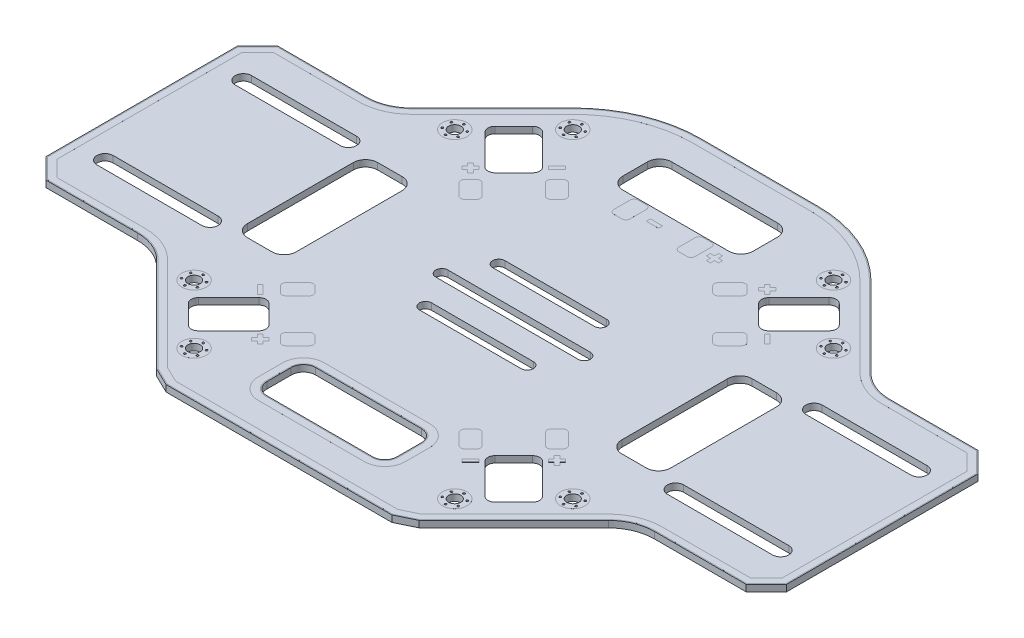
SolidWorks part; units mm, degrees
material "PLA"
ref_plane "Front Plane" through (0, 0, 0) normal (0, 0, 1) x (1, 0, 0)
ref_plane "Top Plane" through (0, 0, 0) normal (0, 1, 0) x (1, 0, 0)
ref_plane "Right Plane" through (0, 0, 0) normal (1, 0, 0) x (0, 0, -1)
sketch "Sketch1" plane through (0, 0, 0) normal (0, 1, 0) x (1, 0, 0)
  line L0 (0, 60.3186) -> (0, -57.6814) construction
  line L1 (-27.75, -57.6814) -> (27.75, -57.6814)
  line L2 (-13, -47.6814) -> (13, -47.6814)
  line L3 (-16, -38.6814) -> (-16, -44.6814)
  line L4 (16, -38.6814) -> (16, -44.6814)
  line L5 (-16, -41.6814) -> (16, -41.6814) construction
  line L6 (-13, -35.6814) -> (13, -35.6814)
  line L7 (-27.75, -57.6814) -> (-32.25, -55.502)
  line L8 (27.75, -57.6814) -> (32.25, -55.502)
  line L9 (-32.25, -55.502) -> (32.25, -55.502) construction
  line L10 (32.25, -55.502) -> (55.502, -32.25)
  line L11 (-32.25, -55.502) -> (-55.502, -32.25)
  line L12 (-43.876, 43.876) -> (43.876, -43.876) construction
  line L13 (-43.876, -43.876) -> (43.876, 43.876) construction
  line L14 (37.6888, -42.285) -> (42.285, -37.6888)
  line L15 (27.7893, -34.8604) -> (35.2139, -42.285)
  line L16 (34.8604, -27.7893) -> (42.285, -35.2139)
  line L17 (31.5016, -38.5727) -> (38.5727, -31.5016) construction
  line L18 (27.7893, -32.3855) -> (32.3855, -27.7893)
  line L19 (-38.5727, -31.5016) -> (-31.5016, -38.5727) construction
  line L20 (-35.2139, -42.285) -> (-27.7893, -34.8604)
  line L21 (-42.285, -35.2139) -> (-34.8604, -27.7893)
  line L22 (-32.3855, -27.7893) -> (-27.7893, -32.3855)
  line L23 (-42.285, -37.6888) -> (-37.6888, -42.285)
  line L24 (-63.5, -28.9371) -> (63.5, -28.9371) construction
  line L25 (63.5, -28.9371) -> (86, -28.9371)
  line L26 (-63.5, -28.9371) -> (-86, -28.9371)
  line L27 (-91, -23.9371) -> (-91, 23.0629)
  line L28 (91, -23.9371) -> (91, 23.0629)
  line L29 (-86, -28.9371) -> (-86, 28.0629) construction
  line L30 (86, -28.9371) -> (86, 28.0629) construction
  line L31 (-91, -0.4371) -> (-86, -0.4371) construction
  line L32 (86, -0.4371) -> (91, -0.4371) construction
  line L33 (86, -28.9371) -> (91, -23.9371)
  line L34 (-91, -23.9371) -> (-86, -28.9371)
  line L35 (91, 23.0629) -> (86, 28.0629)
  line L36 (-91, 23.0629) -> (-86, 28.0629)
  line L37 (-56.4271, 31.3248) -> (-36.6281, 51.1238)
  line L38 (36.6281, 51.1238) -> (56.4271, 31.3248)
  line L39 (-35.2139, 42.285) -> (-27.7893, 34.8604)
  line L40 (-36.6281, 51.1238) -> (-27.7893, 42.285) construction
  line L41 (-27.7893, 42.285) -> (-31.5016, 38.5727) construction
  line L42 (-42.285, 35.2139) -> (-34.8604, 27.7893)
  line L43 (-31.5016, 38.5727) -> (-38.5727, 31.5016) construction
  line L44 (-42.285, 37.6888) -> (-37.6888, 42.285)
  line L45 (-32.3855, 27.7893) -> (-27.7893, 32.3855)
  line L46 (-86, 28.0629) -> (-64.3021, 28.0629)
  line L47 (86, 28.0629) -> (64.3021, 28.0629)
  line L48 (37.6888, 42.285) -> (42.285, 37.6888)
  line L49 (27.7893, 32.3855) -> (32.3855, 27.7893)
  line L50 (27.7893, 34.8604) -> (35.2139, 42.285)
  line L51 (34.8604, 27.7893) -> (42.285, 35.2139)
  line L52 (31.5016, 38.5727) -> (38.5727, 31.5016) construction
  line L53 (31.5016, 38.5727) -> (27.7893, 42.285) construction
  line L54 (27.7893, 42.285) -> (36.6281, 51.1238) construction
  line L55 (-14.43, 60.3186) -> (14.43, 60.3186)
  line L56 (-13, 51.8186) -> (13, 51.8186)
  line L57 (-13, 39.8186) -> (13, 39.8186)
  line L58 (16, 48.8186) -> (16, 42.8186)
  line L59 (-16, 48.8186) -> (-16, 42.8186)
  line L60 (-12.5, -10.6814) -> (12.5, -10.6814)
  line L61 (-12.5, -7.6814) -> (12.5, -7.6814)
  line L62 (-17.5, -1.6814) -> (17.5, -1.6814)
  line L63 (-17.5, 1.3186) -> (17.5, 1.3186)
  line L64 (-12.5, 7.3186) -> (12.5, 7.3186)
  line L65 (-12.5, 10.3186) -> (12.5, 10.3186)
  line L66 (-52, 12.5629) -> (-52, -13.4371)
  line L67 (-86, -0.4371) -> (-52, -0.4371) construction
  line L68 (-40, 12.5629) -> (-40, -13.4371)
  line L69 (52, 12.5629) -> (52, -13.4371)
  line L70 (-49, 15.5629) -> (-43, 15.5629)
  line L71 (-49, -16.4371) -> (-43, -16.4371)
  line L72 (86, -0.4371) -> (52, -0.4371) construction
  line L73 (40, 12.5629) -> (40, -13.4371)
  line L74 (43, 15.5629) -> (49, 15.5629)
  line L75 (43, -16.4371) -> (49, -16.4371)
  line L76 (-83, 18.5629) -> (-57.2, 18.5629)
  line L77 (-83, 14.5629) -> (-57.2, 14.5629)
  line L78 (-83, -15.4371) -> (-57.2, -15.4371)
  line L79 (-83, -19.4371) -> (-57.2, -19.4371)
  line L80 (57.2, -15.4371) -> (83, -15.4371)
  line L81 (57.2, -19.4371) -> (83, -19.4371)
  line L82 (57.2, 18.5629) -> (83, 18.5629)
  line L83 (57.2, 14.5629) -> (83, 14.5629)
  line L84 (-46.5276, 32.0319) -> (-32.0319, 46.5276) construction
  line L85 (32.0319, -46.5276) -> (46.5276, -32.0319) construction
  arc A0 (-16, -44.6814) -> (-13, -47.6814) centre (-13, -44.6814) ccw
  arc A1 (-13, -35.6814) -> (-16, -38.6814) centre (-13, -38.6814) ccw
  arc A2 (16, -38.6814) -> (13, -35.6814) centre (13, -38.6814) ccw
  arc A3 (13, -47.6814) -> (16, -44.6814) centre (13, -44.6814) ccw
  arc A4 (27.7893, -32.3855) -> (27.7893, -34.8604) centre (29.0267, -33.6229) ccw
  arc A5 (34.8604, -27.7893) -> (32.3855, -27.7893) centre (33.6229, -29.0267) ccw
  arc A6 (35.2139, -42.285) -> (37.6888, -42.285) centre (36.4514, -41.0475) ccw
  arc A7 (42.285, -37.6888) -> (42.285, -35.2139) centre (41.0475, -36.4514) ccw
  arc A8 (-37.6888, -42.285) -> (-35.2139, -42.285) centre (-36.4514, -41.0475) ccw
  arc A9 (-42.285, -35.2139) -> (-42.285, -37.6888) centre (-41.0475, -36.4514) ccw
  arc A10 (-32.3855, -27.7893) -> (-34.8604, -27.7893) centre (-33.6229, -29.0267) ccw
  arc A11 (-27.7893, -34.8604) -> (-27.7893, -32.3855) centre (-29.0267, -33.6229) ccw
  arc A12 (-55.502, -32.25) -> (-63.5, -28.9371) centre (-63.5, -40.248) ccw
  arc A13 (63.5, -28.9371) -> (55.502, -32.25) centre (63.5, -40.248) ccw
  arc A14 (-42.285, 37.6888) -> (-42.285, 35.2139) centre (-41.0475, 36.4514) ccw
  arc A15 (-35.2139, 42.285) -> (-37.6888, 42.285) centre (-36.4514, 41.0475) ccw
  arc A16 (-27.7893, 32.3855) -> (-27.7893, 34.8604) centre (-29.0267, 33.6229) ccw
  arc A17 (-34.8604, 27.7893) -> (-32.3855, 27.7893) centre (-33.6229, 29.0267) ccw
  arc A18 (-64.3021, 28.0629) -> (-56.4271, 31.3248) centre (-64.3021, 39.1998) ccw
  arc A19 (56.4271, 31.3248) -> (64.3021, 28.0629) centre (64.3021, 39.1998) ccw
  arc A20 (27.7893, 34.8604) -> (27.7893, 32.3855) centre (29.0267, 33.6229) ccw
  arc A21 (37.6888, 42.285) -> (35.2139, 42.285) centre (36.4514, 41.0475) ccw
  arc A22 (42.285, 35.2139) -> (42.285, 37.6888) centre (41.0475, 36.4514) ccw
  arc A23 (32.3855, 27.7893) -> (34.8604, 27.7893) centre (33.6229, 29.0267) ccw
  arc A24 (-14.43, 60.3186) -> (-36.6281, 51.1238) centre (-14.43, 28.9257) ccw
  arc A25 (13, 39.8186) -> (16, 42.8186) centre (13, 42.8186) ccw
  arc A26 (36.6281, 51.1238) -> (14.43, 60.3186) centre (14.43, 28.9257) ccw
  arc A27 (16, 48.8186) -> (13, 51.8186) centre (13, 48.8186) ccw
  arc A28 (-16, 42.8186) -> (-13, 39.8186) centre (-13, 42.8186) ccw
  arc A29 (-13, 51.8186) -> (-16, 48.8186) centre (-13, 48.8186) ccw
  arc A30 (-12.5, -7.6814) -> (-12.5, -10.6814) centre (-12.5, -9.1814) ccw
  arc A31 (12.5, -10.6814) -> (12.5, -7.6814) centre (12.5, -9.1814) ccw
  arc A32 (-17.5, 1.3186) -> (-17.5, -1.6814) centre (-17.5, -0.1814) ccw
  arc A33 (17.5, -1.6814) -> (17.5, 1.3186) centre (17.5, -0.1814) ccw
  arc A34 (-12.5, 10.3186) -> (-12.5, 7.3186) centre (-12.5, 8.8186) ccw
  arc A35 (12.5, 7.3186) -> (12.5, 10.3186) centre (12.5, 8.8186) ccw
  arc A36 (-49, 15.5629) -> (-52, 12.5629) centre (-49, 12.5629) ccw
  arc A37 (-40, 12.5629) -> (-43, 15.5629) centre (-43, 12.5629) ccw
  arc A38 (-52, -13.4371) -> (-49, -16.4371) centre (-49, -13.4371) ccw
  arc A39 (-43, -16.4371) -> (-40, -13.4371) centre (-43, -13.4371) ccw
  arc A40 (43, 15.5629) -> (40, 12.5629) centre (43, 12.5629) ccw
  arc A41 (52, 12.5629) -> (49, 15.5629) centre (49, 12.5629) ccw
  arc A42 (40, -13.4371) -> (43, -16.4371) centre (43, -13.4371) ccw
  arc A43 (49, -16.4371) -> (52, -13.4371) centre (49, -13.4371) ccw
  arc A44 (-57.2, 14.5629) -> (-57.2, 18.5629) centre (-57.2, 16.5629) ccw
  arc A45 (-83, 18.5629) -> (-83, 14.5629) centre (-83, 16.5629) ccw
  arc A46 (-83, -15.4371) -> (-83, -19.4371) centre (-83, -17.4371) ccw
  arc A47 (-57.2, -19.4371) -> (-57.2, -15.4371) centre (-57.2, -17.4371) ccw
  arc A48 (57.2, -15.4371) -> (57.2, -19.4371) centre (57.2, -17.4371) ccw
  arc A49 (83, -19.4371) -> (83, -15.4371) centre (83, -17.4371) ccw
  arc A50 (57.2, 18.5629) -> (57.2, 14.5629) centre (57.2, 16.5629) ccw
  arc A51 (83, 14.5629) -> (83, 18.5629) centre (83, 16.5629) ccw
  circle A52 centre (-32.0319, 46.5276) radius 1.5
  circle A53 centre (-46.5276, 32.0319) radius 1.5
  circle A54 centre (32.0319, -46.5276) radius 1.5
  circle A55 centre (46.5276, -32.0319) radius 1.5
  circle A56 centre (-46.5276, -32.0319) radius 1.5
  circle A57 centre (-32.0319, -46.5276) radius 1.5
  circle A58 centre (32.0319, 46.5276) radius 1.5
  circle A59 centre (46.5276, 32.0319) radius 1.5
  point P4 (-35.0371, 35.0371)
  point P5 (0, -47.6814)
  point P14 (0, -41.6814)
  point P15 (0, -35.6814)
  point P19 (0, -55.502)
  point P29 (0, 0)
  point P30 (39.9869, -39.9869)
  point P32 (0, 0)
  point P42 (30.0874, -30.0874)
  point P43 (35.0371, -35.0371)
  point P50 (-35.0371, -35.0371)
  point P53 (-38.5727, -31.5016)
  point P62 (-39.9869, -39.9869)
  point P63 (-30.0874, -30.0874)
  point P70 (0, -28.9371)
  point P99 (-39.9869, 39.9869)
  point P102 (-30.0874, 30.0874)
  point P119 (35.0371, 35.0371)
  point P122 (39.9869, 39.9869)
  point P123 (30.0874, 30.0874)
  point P135 (0, 51.8186)
  point P138 (0, 39.8186)
  point P147 (0, -10.6814)
  point P151 (-14, -9.1814)
  point P153 (14, -9.1814)
  point P156 (0, -1.6814)
  point P158 (-19, -0.1814)
  point P162 (19, -0.1814)
  point P167 (0, 7.3186)
  point P203 (-85, 16.5629)
  point P205 (-55.2, 16.5629)
  point P217 (85, -17.4371)
  point P229 (-39.2798, 39.2798)
  point P232 (39.2798, -39.2798)
  dimension "D5" = 12
  dimension "D6" = 55.5
  dimension "D14" = 14
  dimension "D15" = 127
  dimension "D16" = 22.5
  dimension "D23" = 8.5
  dimension "D24" = 25
  dimension "D25" = 3
  dimension "D28" = 3
  dimension "D31" = 39
  dimension "D32" = 9.5
  dimension "D34" = 29.8
  dimension "D38" = 6
  dimension "D39" = 3
  dimension "D1" = 118
  dimension "D2" = 10
  dimension "D3" = 32
  dimension "D4" = 6
  dimension "D7" = 64.5
  dimension "D8" = 5
  dimension "D9" = 124.1
  dimension "D10" = 45
  dimension "D11" = 5.5
  dimension "D12" = 6.5
  dimension "D13" = 10
  dimension "D17" = 22.5
  dimension "D18" = 5
  dimension "D19" = 45
  dimension "D20" = 47
  dimension "D21" = 28
  dimension "D22" = 5.25
  dimension "D26" = 28
  dimension "D27" = 6
  dimension "D29" = 38
  dimension "D30" = 6
  dimension "D33" = 4
  dimension "D35" = 6
  dimension "D36" = 9.5
  dimension "D37" = 4
  dimension "D40" = 6.5
  dimension "D41" = 6.5
extrude "Boss-Extrude1" add sketch "Sketch1" along normal blind 0.8 and the other way blind 0.8
sketch "Sketch2" plane through (0, 0.8, 0) normal (0, 1, 0) x (1, 0, 0)
  line L0 (-27.6926, -57.4314) -> (27.6926, -57.4314)
  line L1 (-27.75, -57.6814) -> (27.75, -57.6814) construction
  line L2 (-27.6926, -57.4314) -> (-32.1031, -55.2953)
  line L3 (-32.25, -55.502) -> (-27.75, -57.6814) construction
  line L4 (27.6926, -57.4314) -> (32.1031, -55.2953)
  line L5 (27.75, -57.6814) -> (32.25, -55.502) construction
  line L6 (0, -57.6814) -> (0, -57.4314) construction
  line L7 (-32.1031, -55.2953) -> (-55.3252, -32.0732)
  line L8 (-55.502, -32.25) -> (-32.25, -55.502) construction
  line L9 (32.1031, -55.2953) -> (55.3252, -32.0732)
  line L10 (32.25, -55.502) -> (55.502, -32.25) construction
  line L11 (-85.8964, -28.6871) -> (-63.5, -28.6871)
  line L12 (-85.8964, -28.6871) -> (-90.75, -23.8335)
  line L13 (-91, -23.9371) -> (-86, -28.9371) construction
  line L14 (-86, -28.9371) -> (-63.5, -28.9371) construction
  line L15 (63.5, -28.6871) -> (85.8964, -28.6871)
  line L16 (85.8964, -28.6871) -> (90.75, -23.8335)
  line L17 (-90.75, -23.8335) -> (-90.75, 22.9593)
  line L18 (-91, 23.0629) -> (-91, -23.9371) construction
  line L19 (-90.75, 22.9593) -> (-85.8964, 27.8129)
  line L20 (-85.8964, 27.8129) -> (-64.3021, 27.8129)
  line L21 (-64.3021, 28.0629) -> (-86, 28.0629) construction
  line L22 (-56.2503, 31.1481) -> (-36.4514, 50.947)
  line L23 (-36.6281, 51.1238) -> (-56.4271, 31.3248) construction
  line L24 (-14.43, 60.0686) -> (14.43, 60.0686)
  line L25 (14.43, 60.3186) -> (-14.43, 60.3186) construction
  line L26 (56.2503, 31.1481) -> (36.4514, 50.947)
  line L27 (56.4271, 31.3248) -> (36.6281, 51.1238) construction
  line L28 (64.3021, 27.8129) -> (85.8964, 27.8129)
  line L29 (86, 28.0629) -> (64.3021, 28.0629) construction
  line L30 (85.8964, 27.8129) -> (90.75, 22.9593)
  line L31 (91, 23.0629) -> (86, 28.0629) construction
  line L32 (90.75, 22.9593) -> (90.75, -23.8335)
  line L33 (-55.0836, 29.9813) -> (-35.2846, 49.7803)
  line L34 (-14.43, 58.4186) -> (14.43, 58.4186)
  line L35 (55.0836, 29.9813) -> (35.2846, 49.7803)
  line L36 (64.3021, 26.1629) -> (85.213, 26.1629)
  line L37 (85.213, 26.1629) -> (89.1, 22.2759)
  line L38 (89.1, 22.2759) -> (89.1, -23.1501)
  line L39 (85.213, -27.0371) -> (89.1, -23.1501)
  line L40 (63.5, -27.0371) -> (85.213, -27.0371)
  line L41 (31.1332, -53.9317) -> (54.1584, -30.9065)
  line L42 (27.3141, -55.7814) -> (31.1332, -53.9317)
  line L43 (-27.3141, -55.7814) -> (27.3141, -55.7814)
  line L44 (-27.3141, -55.7814) -> (-31.1332, -53.9317)
  line L45 (-31.1332, -53.9317) -> (-54.1584, -30.9065)
  line L46 (-85.213, -27.0371) -> (-63.5, -27.0371)
  line L47 (-85.213, -27.0371) -> (-89.1, -23.1501)
  line L48 (-89.1, -23.1501) -> (-89.1, 22.2759)
  line L49 (-89.1, 22.2759) -> (-85.213, 26.1629)
  line L50 (-85.213, 26.1629) -> (-64.3021, 26.1629)
  line L51 (-13, -35.4314) -> (13, -35.4314)
  line L52 (-16.25, -38.6814) -> (-16.25, -44.6814)
  line L53 (-13, -47.9314) -> (13, -47.9314)
  line L54 (16.25, -44.6814) -> (16.25, -38.6814)
  line L55 (16, -44.6814) -> (16, -38.6814) construction
  line L56 (13, -35.6814) -> (-13, -35.6814) construction
  line L57 (-16, -38.6814) -> (-16, -44.6814) construction
  line L58 (-13, -47.6814) -> (13, -47.6814) construction
  line L59 (-13, -33.6314) -> (13, -33.6314)
  line L60 (18.05, -44.6814) -> (18.05, -38.6814)
  line L61 (-13, -49.7314) -> (13, -49.7314)
  line L62 (-18.05, -38.6814) -> (-18.05, -44.6814)
  line L63 (32.0319, -43.5276) -> (32.0319, -44.2776) construction
  line L64 (-32.0319, -44.2776) -> (-33.9805, -45.4026) construction
  line L65 (-33.9805, -45.4026) -> (-33.9805, -47.6526) construction
  line L66 (-33.9805, -47.6526) -> (-32.0319, -48.7776) construction
  line L67 (-32.0319, -48.7776) -> (-30.0834, -47.6526) construction
  line L68 (-30.0834, -47.6526) -> (-30.0834, -45.4026) construction
  line L69 (-30.0834, -45.4026) -> (-32.0319, -44.2776) construction
  line L70 (-46.5276, -29.7819) -> (-48.4762, -30.9069) construction
  line L71 (-48.4762, -30.9069) -> (-48.4762, -33.1569) construction
  line L72 (-48.4762, -33.1569) -> (-46.5276, -34.2819) construction
  line L73 (-46.5276, -34.2819) -> (-44.5791, -33.1569) construction
  line L74 (-44.5791, -33.1569) -> (-44.5791, -30.9069) construction
  line L75 (-44.5791, -30.9069) -> (-46.5276, -29.7819) construction
  line L76 (-46.5276, 34.2819) -> (-48.4762, 33.1569) construction
  line L77 (-48.4762, 33.1569) -> (-48.4762, 30.9069) construction
  line L78 (-48.4762, 30.9069) -> (-46.5276, 29.7819) construction
  line L79 (-46.5276, 29.7819) -> (-44.5791, 30.9069) construction
  line L80 (-44.5791, 30.9069) -> (-44.5791, 33.1569) construction
  line L81 (-44.5791, 33.1569) -> (-46.5276, 34.2819) construction
  line L82 (-32.0319, 48.7776) -> (-33.9805, 47.6526) construction
  line L83 (-33.9805, 47.6526) -> (-33.9805, 45.4026) construction
  line L84 (-33.9805, 45.4026) -> (-32.0319, 44.2776) construction
  line L85 (-32.0319, 44.2776) -> (-30.0834, 45.4026) construction
  line L86 (-30.0834, 45.4026) -> (-30.0834, 47.6526) construction
  line L87 (-30.0834, 47.6526) -> (-32.0319, 48.7776) construction
  line L88 (32.0319, 48.7776) -> (30.0834, 47.6526) construction
  line L89 (30.0834, 47.6526) -> (30.0834, 45.4026) construction
  line L90 (30.0834, 45.4026) -> (32.0319, 44.2776) construction
  line L91 (32.0319, 44.2776) -> (33.9805, 45.4026) construction
  line L92 (33.9805, 45.4026) -> (33.9805, 47.6526) construction
  line L93 (33.9805, 47.6526) -> (32.0319, 48.7776) construction
  line L94 (46.5276, 34.2819) -> (44.5791, 33.1569) construction
  line L95 (44.5791, 33.1569) -> (44.5791, 30.9069) construction
  line L96 (44.5791, 30.9069) -> (46.5276, 29.7819) construction
  line L97 (46.5276, 29.7819) -> (48.4762, 30.9069) construction
  line L98 (48.4762, 30.9069) -> (48.4762, 33.1569) construction
  line L99 (48.4762, 33.1569) -> (46.5276, 34.2819) construction
  line L100 (46.5276, -29.7819) -> (44.5791, -30.9069) construction
  line L101 (44.5791, -30.9069) -> (44.5791, -33.1569) construction
  line L102 (44.5791, -33.1569) -> (46.5276, -34.2819) construction
  line L103 (46.5276, -34.2819) -> (48.4762, -33.1569) construction
  line L104 (48.4762, -33.1569) -> (48.4762, -30.9069) construction
  line L105 (48.4762, -30.9069) -> (46.5276, -29.7819) construction
  line L106 (32.0319, -44.2776) -> (30.0834, -45.4026) construction
  line L107 (30.0834, -45.4026) -> (30.0834, -47.6526) construction
  line L108 (30.0834, -47.6526) -> (32.0319, -48.7776) construction
  line L109 (32.0319, -48.7776) -> (33.9805, -47.6526) construction
  line L110 (33.9805, -47.6526) -> (33.9805, -45.4026) construction
  line L111 (33.9805, -45.4026) -> (32.0319, -44.2776) construction
  line L112 (32.0319, -44.2776) -> (32.0319, -45.0276) construction
  arc A0 (-55.3252, -32.0732) -> (-63.5, -28.6871) centre (-63.5, -40.248) ccw
  arc A1 (-55.502, -32.25) -> (-63.5, -28.9371) centre (-63.5, -40.248) ccw construction
  arc A2 (63.5, -28.6871) -> (55.3252, -32.0732) centre (63.5, -40.248) ccw
  arc A3 (63.5, -28.9371) -> (55.502, -32.25) centre (63.5, -40.248) ccw construction
  arc A4 (-64.3021, 27.8129) -> (-56.2503, 31.1481) centre (-64.3021, 39.1998) ccw
  arc A5 (-64.3021, 28.0629) -> (-56.4271, 31.3248) centre (-64.3021, 39.1998) ccw construction
  arc A6 (-14.43, 60.0686) -> (-36.4514, 50.947) centre (-14.43, 28.9257) ccw
  arc A7 (-14.43, 60.3186) -> (-36.6281, 51.1238) centre (-14.43, 28.9257) ccw construction
  arc A8 (36.4514, 50.947) -> (14.43, 60.0686) centre (14.43, 28.9257) ccw
  arc A9 (36.6281, 51.1238) -> (14.43, 60.3186) centre (14.43, 28.9257) ccw construction
  arc A10 (56.2503, 31.1481) -> (64.3021, 27.8129) centre (64.3021, 39.1998) ccw
  arc A11 (56.4271, 31.3248) -> (64.3021, 28.0629) centre (64.3021, 39.1998) ccw construction
  arc A12 (-14.43, 58.4186) -> (-35.2846, 49.7803) centre (-14.43, 28.9257) ccw
  arc A13 (35.2846, 49.7803) -> (14.43, 58.4186) centre (14.43, 28.9257) ccw
  arc A14 (55.0836, 29.9813) -> (64.3021, 26.1629) centre (64.3021, 39.1998) ccw
  arc A15 (63.5, -27.0371) -> (54.1584, -30.9065) centre (63.5, -40.248) ccw
  arc A16 (-54.1584, -30.9065) -> (-63.5, -27.0371) centre (-63.5, -40.248) ccw
  arc A17 (-64.3021, 26.1629) -> (-55.0836, 29.9813) centre (-64.3021, 39.1998) ccw
  arc A18 (-13, -35.4314) -> (-16.25, -38.6814) centre (-13, -38.6814) ccw
  arc A19 (16.25, -38.6814) -> (13, -35.4314) centre (13, -38.6814) ccw
  arc A20 (-16.25, -44.6814) -> (-13, -47.9314) centre (-13, -44.6814) ccw
  arc A21 (13, -47.9314) -> (16.25, -44.6814) centre (13, -44.6814) ccw
  arc A22 (-13, -35.6814) -> (-16, -38.6814) centre (-13, -38.6814) ccw construction
  arc A23 (-16, -44.6814) -> (-13, -47.6814) centre (-13, -44.6814) ccw construction
  arc A24 (16, -38.6814) -> (13, -35.6814) centre (13, -38.6814) ccw construction
  arc A25 (13, -47.6814) -> (16, -44.6814) centre (13, -44.6814) ccw construction
  arc A26 (18.05, -38.6814) -> (13, -33.6314) centre (13, -38.6814) ccw
  arc A27 (13, -49.7314) -> (18.05, -44.6814) centre (13, -44.6814) ccw
  arc A28 (-18.05, -44.6814) -> (-13, -49.7314) centre (-13, -44.6814) ccw
  arc A29 (-13, -33.6314) -> (-18.05, -38.6814) centre (-13, -38.6814) ccw
  circle A30 centre (-32.0319, -46.5276) radius 1.5
  circle A31 centre (-46.5276, -32.0319) radius 1.5
  circle A32 centre (-46.5276, 32.0319) radius 1.5
  circle A33 centre (-32.0319, 46.5276) radius 1.5
  circle A34 centre (32.0319, 46.5276) radius 1.5
  circle A35 centre (46.5276, 32.0319) radius 1.5
  circle A36 centre (46.5276, -32.0319) radius 1.5
  circle A37 centre (32.0319, -46.5276) radius 1.5
  circle A38 centre (-32.0319, -46.5276) radius 1.5 construction
  circle A39 centre (-46.5276, -32.0319) radius 1.5 construction
  circle A40 centre (-46.5276, 32.0319) radius 1.5 construction
  circle A41 centre (-32.0319, 46.5276) radius 1.5 construction
  circle A42 centre (32.0319, 46.5276) radius 1.5 construction
  circle A43 centre (46.5276, 32.0319) radius 1.5 construction
  circle A44 centre (46.5276, -32.0319) radius 1.5 construction
  circle A45 centre (32.0319, -46.5276) radius 1.5 construction
  circle A46 centre (-32.0319, -46.5276) radius 3
  circle A47 centre (-46.5276, -32.0319) radius 3
  circle A48 centre (-46.5276, 32.0319) radius 3
  circle A49 centre (-32.0319, 46.5276) radius 3
  circle A50 centre (32.0319, 46.5276) radius 3
  circle A51 centre (46.5276, 32.0319) radius 3
  circle A52 centre (46.5276, -32.0319) radius 3
  circle A53 centre (32.0319, -46.5276) radius 3
  circle A54 centre (-32.0319, -46.5276) radius 1.9486 construction
  circle A55 centre (-46.5276, -32.0319) radius 1.9486 construction
  circle A56 centre (-46.5276, 32.0319) radius 1.9486 construction
  circle A57 centre (-32.0319, 46.5276) radius 1.9486 construction
  circle A58 centre (32.0319, 46.5276) radius 1.9486 construction
  circle A59 centre (46.5276, 32.0319) radius 1.9486 construction
  circle A60 centre (46.5276, -32.0319) radius 1.9486 construction
  circle A61 centre (32.0319, -46.5276) radius 1.9486 construction
  circle A62 centre (32.0319, -44.2776) radius 0.25
  circle A63 centre (33.9805, -45.4026) radius 0.25
  circle A64 centre (33.9805, -47.6526) radius 0.25
  circle A65 centre (32.0319, -48.7776) radius 0.25
  circle A66 centre (30.0834, -47.6526) radius 0.25
  circle A67 centre (30.0834, -45.4026) radius 0.25
  circle A68 centre (46.5276, -34.2819) radius 0.25
  circle A69 centre (48.4762, -33.1569) radius 0.25
  circle A70 centre (48.4762, -30.9069) radius 0.25
  circle A71 centre (46.5276, -29.7819) radius 0.25
  circle A72 centre (44.5791, -30.9069) radius 0.25
  circle A73 centre (44.5791, -33.1569) radius 0.25
  circle A74 centre (46.5276, 29.7819) radius 0.25
  circle A75 centre (48.4762, 30.9069) radius 0.25
  circle A76 centre (48.4762, 33.1569) radius 0.25
  circle A77 centre (46.5276, 34.2819) radius 0.25
  circle A78 centre (44.5791, 33.1569) radius 0.25
  circle A79 centre (44.5791, 30.9069) radius 0.25
  circle A80 centre (32.0319, 44.2776) radius 0.25
  circle A81 centre (33.9805, 45.4026) radius 0.25
  circle A82 centre (33.9805, 47.6526) radius 0.25
  circle A83 centre (32.0319, 48.7776) radius 0.25
  circle A84 centre (30.0834, 47.6526) radius 0.25
  circle A85 centre (30.0834, 45.4026) radius 0.25
  circle A86 centre (-32.0319, 48.7776) radius 0.25
  circle A87 centre (-30.0834, 47.6526) radius 0.25
  circle A88 centre (-30.0834, 45.4026) radius 0.25
  circle A89 centre (-32.0319, 44.2776) radius 0.25
  circle A90 centre (-33.9805, 47.6526) radius 0.25
  circle A91 centre (-33.9805, 45.4026) radius 0.25
  circle A92 centre (-46.5276, 29.7819) radius 0.25
  circle A93 centre (-44.5791, 30.9069) radius 0.25
  circle A94 centre (-44.5791, 33.1569) radius 0.25
  circle A95 centre (-46.5276, 34.2819) radius 0.25
  circle A96 centre (-48.4762, 33.1569) radius 0.25
  circle A97 centre (-48.4762, 30.9069) radius 0.25
  circle A98 centre (-46.5276, -29.7819) radius 0.25
  circle A99 centre (-44.5791, -30.9069) radius 0.25
  circle A100 centre (-44.5791, -33.1569) radius 0.25
  circle A101 centre (-46.5276, -34.2819) radius 0.25
  circle A102 centre (-48.4762, -33.1569) radius 0.25
  circle A103 centre (-48.4762, -30.9069) radius 0.25
  circle A104 centre (-32.0319, -44.2776) radius 0.25
  circle A105 centre (-30.0834, -45.4026) radius 0.25
  circle A106 centre (-30.0834, -47.6526) radius 0.25
  circle A107 centre (-32.0319, -48.7776) radius 0.25
  circle A108 centre (-33.9805, -47.6526) radius 0.25
  circle A109 centre (-33.9805, -45.4026) radius 0.25
  dimension "D2" = 0.25
  dimension "D5" = 0.25
  dimension "D7" = 1.65
  dimension "D8" = 0.25
  dimension "D10" = 6
  dimension "D11" = 0.5
  dimension "D1" = 0.25
  dimension "D3" = 0.25
  dimension "D4" = 0.25
  dimension "D6" = 0.25
  dimension "D9" = 1.8
extrude "Boss-Extrude2" add sketch "Sketch2" along normal blind 0.001 contours A10 L26 A8 L24 A6 L22 A4 L20 L19 L17 L12 L11 A0 L7 L2 L0 L4 L9 A2 L15 L16 L32 L30 L28 L50 A17 L33 A12 L34 A13 L35 A14 L36 L37 L38 L39 L40 A15 L41 L42 L43 L44 L45 A16 L46 L47 L48 L49 | A46 A109 A108 A107 A106 A105 A104 A30 | A47 A103 A102 A101 A100 A99 A98 A31 | A48 A97 A96 A95 A94 A93 A92 A32 | A49 A91 A90 A89 A88 A87 A86 A33 | A50 A85 A84 A83 A82 A81 A80 A34 | A51 A79 A78 A77 A76 A75 A74 A35 | A52 A73 A72 A71 A70 A69 A68 A36 | A53 A67 A66 A65 A64 A63 A62 A37 | L59 A29 L62 A28 L61 A27 L60 A26 A21 L53 A20 L52 A18 L51 A19 L54 region at (-29.8036, 0.8, 56.1688) region at (0, 0.8, 34.0267) region at (-34.9471, 0.8, 46.5276) region at (-49.4428, 0.8, 32.0319) region at (-49.4428, 0.8, -32.0319) region at (-34.9471, 0.8, -46.5276) region at (29.1168, 0.8, -46.5276) region at (43.6125, 0.8, -32.0319) region at (43.6125, 0.8, 32.0319) region at (29.1168, 0.8, 46.5276)
mirror "Mirror1" about plane through (0, 0, 0) normal (0, 1, 0) of "Boss-Extrude2"
sketch "Sketch5" plane through (0, 0.8, 0) normal (0, 1, 0) x (1, 0, 0)
  line L0 (35.7442, -27.259) -> (36.4514, -26.5519)
  line L1 (35.0371, -26.5519) -> (35.7442, -25.8448)
  line L2 (35.3907, -26.9054) -> (37.512, -24.7841) construction
  line L3 (35.0371, -26.5519) -> (35.7442, -27.259)
  line L4 (37.1585, -24.4305) -> (37.8656, -25.1376)
  line L5 (42.285, -35.2139) -> (34.8604, -27.7893) construction
  line L6 (32.1031, -55.2953) -> (55.3252, -32.0732) construction
  line L8 (35.3907, -24.7841) -> (37.512, -26.9054) construction
  line L9 (35.0371, -25.1376) -> (35.7442, -24.4305)
  line L10 (37.1585, -27.259) -> (37.8656, -26.5519)
  line L11 (35.0371, -25.1376) -> (35.7442, -25.8448)
  line L12 (35.7442, -24.4305) -> (36.4514, -25.1376)
  line L13 (36.4514, -26.5519) -> (37.1585, -27.259)
  line L14 (36.4514, -25.1376) -> (37.1585, -24.4305)
  line L15 (37.1585, -25.8448) -> (37.8656, -26.5519)
  line L16 (37.1585, -25.8448) -> (37.8656, -25.1376)
  line L17 (26.9054, -35.3907) -> (24.7841, -37.512) construction
  line L18 (26.5519, -35.0371) -> (27.259, -35.7442)
  line L19 (27.7893, -34.8604) -> (35.2139, -42.285) construction
  line L20 (24.4305, -37.1585) -> (25.1376, -37.8656)
  line L21 (24.4305, -37.1585) -> (26.5519, -35.0371)
  line L22 (25.1376, -37.8656) -> (27.259, -35.7442)
  line L23 (-37.1585, -24.4305) -> (-37.8656, -25.1376)
  line L24 (-37.1585, -24.4305) -> (-35.0371, -26.5519)
  line L25 (-37.8656, -25.1376) -> (-35.7442, -27.259)
  line L26 (-35.3907, -26.9054) -> (-37.512, -24.7841) construction
  line L27 (-35.0371, -26.5519) -> (-35.7442, -27.259)
  line L28 (-26.5519, -35.0371) -> (-27.259, -35.7442)
  line L29 (-27.259, -35.7442) -> (-26.5519, -36.4514)
  line L30 (-26.5519, -36.4514) -> (-27.259, -37.1585)
  line L31 (-27.259, -37.1585) -> (-26.5519, -37.8656)
  line L32 (-25.8448, -37.1585) -> (-26.5519, -37.8656)
  line L33 (-25.8448, -37.1585) -> (-25.1376, -37.8656)
  line L34 (-24.4305, -37.1585) -> (-25.1376, -37.8656)
  line L35 (-25.1376, -36.4514) -> (-24.4305, -37.1585)
  line L36 (-24.4305, -35.7442) -> (-25.1376, -36.4514)
  line L37 (-25.1376, -35.0371) -> (-24.4305, -35.7442)
  line L38 (-25.1376, -35.0371) -> (-25.8448, -35.7442)
  line L39 (-26.5519, -35.0371) -> (-25.8448, -35.7442)
  line L40 (-26.9054, -35.3907) -> (-24.7841, -37.512) construction
  line L41 (-24.7841, -35.3907) -> (-26.9054, -37.512) construction
  line L42 (-24.4305, 37.1585) -> (-25.1376, 37.8656)
  line L43 (-24.4305, 37.1585) -> (-26.5519, 35.0371)
  line L44 (-25.1376, 37.8656) -> (-27.259, 35.7442)
  line L45 (-26.9054, 35.3907) -> (-24.7841, 37.512) construction
  line L46 (-26.5519, 35.0371) -> (-27.259, 35.7442)
  line L47 (-35.0371, 26.5519) -> (-35.7442, 27.259)
  line L48 (-35.7442, 27.259) -> (-36.4514, 26.5519)
  line L49 (-36.4514, 26.5519) -> (-37.1585, 27.259)
  line L50 (-37.1585, 27.259) -> (-37.8656, 26.5519)
  line L51 (-37.1585, 25.8448) -> (-37.8656, 26.5519)
  line L52 (-37.1585, 25.8448) -> (-37.8656, 25.1376)
  line L53 (-37.1585, 24.4305) -> (-37.8656, 25.1376)
  line L54 (-36.4514, 25.1376) -> (-37.1585, 24.4305)
  line L55 (-35.7442, 24.4305) -> (-36.4514, 25.1376)
  line L56 (-35.0371, 25.1376) -> (-35.7442, 24.4305)
  line L57 (-35.0371, 25.1376) -> (-35.7442, 25.8448)
  line L58 (-35.0371, 26.5519) -> (-35.7442, 25.8448)
  line L59 (-35.3907, 26.9054) -> (-37.512, 24.7841) construction
  line L60 (-35.3907, 24.7841) -> (-37.512, 26.9054) construction
  line L61 (37.1585, 24.4305) -> (37.8656, 25.1376)
  line L62 (37.1585, 24.4305) -> (35.0371, 26.5519)
  line L63 (37.8656, 25.1376) -> (35.7442, 27.259)
  line L64 (35.3907, 26.9054) -> (37.512, 24.7841) construction
  line L65 (35.0371, 26.5519) -> (35.7442, 27.259)
  line L66 (26.5519, 35.0371) -> (27.259, 35.7442)
  line L67 (27.259, 35.7442) -> (26.5519, 36.4514)
  line L68 (26.5519, 36.4514) -> (27.259, 37.1585)
  line L69 (27.259, 37.1585) -> (26.5519, 37.8656)
  line L70 (25.8448, 37.1585) -> (26.5519, 37.8656)
  line L71 (25.8448, 37.1585) -> (25.1376, 37.8656)
  line L72 (24.4305, 37.1585) -> (25.1376, 37.8656)
  line L73 (25.1376, 36.4514) -> (24.4305, 37.1585)
  line L74 (24.4305, 35.7442) -> (25.1376, 36.4514)
  line L75 (25.1376, 35.0371) -> (24.4305, 35.7442)
  line L76 (25.1376, 35.0371) -> (25.8448, 35.7442)
  line L77 (26.5519, 35.0371) -> (25.8448, 35.7442)
  line L78 (26.9054, 35.3907) -> (24.7841, 37.512) construction
  line L79 (24.7841, 35.3907) -> (26.9054, 37.512) construction
  line L80 (-36.6281, 51.1238) -> (-56.4271, 31.3248) construction
  line L81 (29.0267, -19.8343) -> (30.4409, -18.4201)
  line L82 (31.8552, -18.4201) -> (34.6836, -21.2486)
  line L83 (29.0267, -21.2486) -> (31.8552, -24.077)
  line L84 (33.2694, -24.077) -> (34.6836, -22.6628)
  line L85 (30.4409, -22.6628) -> (33.2694, -19.8343) construction
  line L86 (29.7338, -19.1272) -> (33.9765, -23.3699) construction
  line L87 (32.3855, -27.7893) -> (27.7893, -32.3855) construction
  line L88 (18.4201, -31.8552) -> (21.2486, -34.6836)
  line L89 (18.4201, -30.4409) -> (19.8343, -29.0267)
  line L90 (21.2486, -29.0267) -> (24.077, -31.8552)
  line L91 (22.6628, -34.6836) -> (24.077, -33.2694)
  line L92 (19.8343, -33.2694) -> (22.6628, -30.4409) construction
  line L93 (19.1272, -29.7338) -> (23.3699, -33.9765) construction
  line L94 (-34.6836, -22.6628) -> (-33.2694, -24.077)
  line L95 (-31.8552, -18.4201) -> (-34.6836, -21.2486)
  line L96 (-30.4409, -18.4201) -> (-29.0267, -19.8343)
  line L97 (-29.0267, -21.2486) -> (-31.8552, -24.077)
  line L98 (-29.7338, -19.1272) -> (-33.9765, -23.3699) construction
  line L99 (-33.2694, -19.8343) -> (-30.4409, -22.6628) construction
  line L100 (-21.2486, -29.0267) -> (-24.077, -31.8552)
  line L101 (-24.077, -33.2694) -> (-22.6628, -34.6836)
  line L102 (-18.4201, -31.8552) -> (-21.2486, -34.6836)
  line L103 (-19.8343, -29.0267) -> (-18.4201, -30.4409)
  line L104 (-19.1272, -29.7338) -> (-23.3699, -33.9765) construction
  line L105 (-22.6628, -30.4409) -> (-19.8343, -33.2694) construction
  line L106 (-22.6628, 34.6836) -> (-24.077, 33.2694)
  line L107 (-18.4201, 31.8552) -> (-21.2486, 34.6836)
  line L108 (-18.4201, 30.4409) -> (-19.8343, 29.0267)
  line L109 (-21.2486, 29.0267) -> (-24.077, 31.8552)
  line L110 (-19.1272, 29.7338) -> (-23.3699, 33.9765) construction
  line L111 (-19.8343, 33.2694) -> (-22.6628, 30.4409) construction
  line L112 (-29.0267, 21.2486) -> (-31.8552, 24.077)
  line L113 (-33.2694, 24.077) -> (-34.6836, 22.6628)
  line L114 (-31.8552, 18.4201) -> (-34.6836, 21.2486)
  line L115 (-29.0267, 19.8343) -> (-30.4409, 18.4201)
  line L116 (-29.7338, 19.1272) -> (-33.9765, 23.3699) construction
  line L117 (-30.4409, 22.6628) -> (-33.2694, 19.8343) construction
  line L118 (34.6836, 22.6628) -> (33.2694, 24.077)
  line L119 (31.8552, 18.4201) -> (34.6836, 21.2486)
  line L120 (30.4409, 18.4201) -> (29.0267, 19.8343)
  line L121 (29.0267, 21.2486) -> (31.8552, 24.077)
  line L122 (29.7338, 19.1272) -> (33.9765, 23.3699) construction
  line L123 (33.2694, 19.8343) -> (30.4409, 22.6628) construction
  line L124 (21.2486, 29.0267) -> (24.077, 31.8552)
  line L125 (24.077, 33.2694) -> (22.6628, 34.6836)
  line L126 (18.4201, 31.8552) -> (21.2486, 34.6836)
  line L127 (19.8343, 29.0267) -> (18.4201, 30.4409)
  line L128 (19.1272, 29.7338) -> (23.3699, 33.9765) construction
  line L129 (22.6628, 30.4409) -> (19.8343, 33.2694) construction
  line L130 (32.25, -55.502) -> (55.502, -32.25) construction
  arc A0 (31.8552, -18.4201) -> (30.4409, -18.4201) centre (31.1481, -19.1272) ccw
  arc A1 (29.0267, -19.8343) -> (29.0267, -21.2486) centre (29.7338, -20.5415) ccw
  arc A2 (31.8552, -24.077) -> (33.2694, -24.077) centre (32.5623, -23.3699) ccw
  arc A3 (34.6836, -22.6628) -> (34.6836, -21.2486) centre (33.9765, -21.9557) ccw
  arc A4 (18.4201, -30.4409) -> (18.4201, -31.8552) centre (19.1272, -31.1481) ccw
  arc A5 (21.2486, -29.0267) -> (19.8343, -29.0267) centre (20.5415, -29.7338) ccw
  arc A6 (24.077, -33.2694) -> (24.077, -31.8552) centre (23.3699, -32.5623) ccw
  arc A7 (21.2486, -34.6836) -> (22.6628, -34.6836) centre (21.9557, -33.9765) ccw
  arc A8 (-33.2694, -24.077) -> (-31.8552, -24.077) centre (-32.5623, -23.3699) ccw
  arc A9 (-34.6836, -21.2486) -> (-34.6836, -22.6628) centre (-33.9765, -21.9557) ccw
  arc A10 (-30.4409, -18.4201) -> (-31.8552, -18.4201) centre (-31.1481, -19.1272) ccw
  arc A11 (-29.0267, -21.2486) -> (-29.0267, -19.8343) centre (-29.7338, -20.5415) ccw
  arc A12 (-24.077, -31.8552) -> (-24.077, -33.2694) centre (-23.3699, -32.5623) ccw
  arc A13 (-22.6628, -34.6836) -> (-21.2486, -34.6836) centre (-21.9557, -33.9765) ccw
  arc A14 (-18.4201, -31.8552) -> (-18.4201, -30.4409) centre (-19.1272, -31.1481) ccw
  arc A15 (-19.8343, -29.0267) -> (-21.2486, -29.0267) centre (-20.5415, -29.7338) ccw
  arc A16 (-24.077, 33.2694) -> (-24.077, 31.8552) centre (-23.3699, 32.5623) ccw
  arc A17 (-21.2486, 34.6836) -> (-22.6628, 34.6836) centre (-21.9557, 33.9765) ccw
  arc A18 (-18.4201, 30.4409) -> (-18.4201, 31.8552) centre (-19.1272, 31.1481) ccw
  arc A19 (-21.2486, 29.0267) -> (-19.8343, 29.0267) centre (-20.5415, 29.7338) ccw
  arc A20 (-31.8552, 24.077) -> (-33.2694, 24.077) centre (-32.5623, 23.3699) ccw
  arc A21 (-34.6836, 22.6628) -> (-34.6836, 21.2486) centre (-33.9765, 21.9557) ccw
  arc A22 (-31.8552, 18.4201) -> (-30.4409, 18.4201) centre (-31.1481, 19.1272) ccw
  arc A23 (-29.0267, 19.8343) -> (-29.0267, 21.2486) centre (-29.7338, 20.5415) ccw
  arc A24 (33.2694, 24.077) -> (31.8552, 24.077) centre (32.5623, 23.3699) ccw
  arc A25 (34.6836, 21.2486) -> (34.6836, 22.6628) centre (33.9765, 21.9557) ccw
  arc A26 (30.4409, 18.4201) -> (31.8552, 18.4201) centre (31.1481, 19.1272) ccw
  arc A27 (29.0267, 21.2486) -> (29.0267, 19.8343) centre (29.7338, 20.5415) ccw
  arc A28 (24.077, 31.8552) -> (24.077, 33.2694) centre (23.3699, 32.5623) ccw
  arc A29 (22.6628, 34.6836) -> (21.2486, 34.6836) centre (21.9557, 33.9765) ccw
  arc A30 (18.4201, 31.8552) -> (18.4201, 30.4409) centre (19.1272, 31.1481) ccw
  arc A31 (19.8343, 29.0267) -> (21.2486, 29.0267) centre (20.5415, 29.7338) ccw
  point P14 (36.4514, -25.8448)
  point P17 (35.3907, -24.7841)
  point P101 (0, 0)
  point P111 (31.8552, -21.2486)
  point P234 (0, 0)
  dimension "D8" = 2
  dimension "D1" = 3
  dimension "D2" = 1
  dimension "D3" = 18
  dimension "D4" = 1
  dimension "D5" = 1
  dimension "D6" = 4
  dimension "D7" = 18
  dimension "D9" = 4
  dimension "D10" = 2
  dimension "D11" = 4
  dimension "D13" = 4
  dimension "D12" = 15
  dimension "D14" = 2
extrude "Boss-Extrude4" add sketch "Sketch5" along normal blind 0.001
sketch "Sketch6" plane through (0, 0.8, 0) normal (0, 1, 0) x (1, 0, 0)
  circle A0 centre (-48.4762, 33.1569) radius 0.25
  circle A1 centre (-46.5276, 34.2819) radius 0.25
  circle A2 centre (-44.5791, 33.1569) radius 0.25
  circle A3 centre (-48.4762, 30.9069) radius 0.25
  circle A4 centre (-46.5276, 29.7819) radius 0.25
  circle A5 centre (-44.5791, 30.9069) radius 0.25
  circle A6 centre (-33.9805, 45.4026) radius 0.25
  circle A7 centre (-32.0319, 48.7776) radius 0.25
  circle A8 centre (-33.9805, 47.6526) radius 0.25
  circle A9 centre (-32.0319, 44.2776) radius 0.25
  circle A10 centre (-30.0834, 47.6526) radius 0.25
  circle A11 centre (-30.0834, 45.4026) radius 0.25
  circle A12 centre (30.0834, 47.6526) radius 0.25
  circle A13 centre (32.0319, 48.7776) radius 0.25
  circle A14 centre (33.9805, 47.6526) radius 0.25
  circle A15 centre (33.9805, 45.4026) radius 0.25
  circle A16 centre (30.0834, 45.4026) radius 0.25
  circle A17 centre (32.0319, 44.2776) radius 0.25
  circle A18 centre (46.5276, 34.2819) radius 0.25
  circle A19 centre (48.4762, 30.9069) radius 0.25
  circle A20 centre (44.5791, 33.1569) radius 0.25
  circle A21 centre (48.4762, 33.1569) radius 0.25
  circle A22 centre (46.5276, 29.7819) radius 0.25
  circle A23 centre (44.5791, 30.9069) radius 0.25
  circle A24 centre (44.5791, -30.9069) radius 0.25
  circle A25 centre (46.5276, -29.7819) radius 0.25
  circle A26 centre (44.5791, -33.1569) radius 0.25
  circle A27 centre (48.4762, -33.1569) radius 0.25
  circle A28 centre (48.4762, -30.9069) radius 0.25
  circle A29 centre (46.5276, -34.2819) radius 0.25
  circle A30 centre (32.0319, -44.2776) radius 0.25
  circle A31 centre (30.0834, -45.4026) radius 0.25
  circle A32 centre (30.0834, -47.6526) radius 0.25
  circle A33 centre (33.9805, -47.6526) radius 0.25
  circle A34 centre (32.0319, -48.7776) radius 0.25
  circle A35 centre (33.9805, -45.4026) radius 0.25
  circle A36 centre (-48.4762, -30.9069) radius 0.25
  circle A37 centre (-44.5791, -30.9069) radius 0.25
  circle A38 centre (-48.4762, -33.1569) radius 0.25
  circle A39 centre (-46.5276, -34.2819) radius 0.25
  circle A40 centre (-44.5791, -33.1569) radius 0.25
  circle A41 centre (-46.5276, -29.7819) radius 0.25
  circle A42 centre (-33.9805, -45.4026) radius 0.25
  circle A43 centre (-32.0319, -44.2776) radius 0.25
  circle A44 centre (-30.0834, -45.4026) radius 0.25
  circle A45 centre (-30.0834, -47.6526) radius 0.25
  circle A46 centre (-33.9805, -47.6526) radius 0.25
  circle A47 centre (-32.0319, -48.7776) radius 0.25
  circle A48 centre (-48.4762, 33.1569) radius 0.25 construction
  circle A49 centre (-46.5276, 34.2819) radius 0.25 construction
  circle A50 centre (-44.5791, 33.1569) radius 0.25 construction
  circle A51 centre (-44.5791, 30.9069) radius 0.25 construction
  circle A52 centre (-46.5276, 29.7819) radius 0.25 construction
  circle A53 centre (-48.4762, 30.9069) radius 0.25 construction
  circle A54 centre (-33.9805, 45.4026) radius 0.25 construction
  circle A55 centre (-33.9805, 47.6526) radius 0.25 construction
  circle A56 centre (-32.0319, 48.7776) radius 0.25 construction
  circle A57 centre (-30.0834, 47.6526) radius 0.25 construction
  circle A58 centre (-30.0834, 45.4026) radius 0.25 construction
  circle A59 centre (-32.0319, 44.2776) radius 0.25 construction
  circle A60 centre (32.0319, 44.2776) radius 0.25 construction
  circle A61 centre (30.0834, 45.4026) radius 0.25 construction
  circle A62 centre (30.0834, 47.6526) radius 0.25 construction
  circle A63 centre (32.0319, 48.7776) radius 0.25 construction
  circle A64 centre (33.9805, 47.6526) radius 0.25 construction
  circle A65 centre (33.9805, 45.4026) radius 0.25 construction
  circle A66 centre (46.5276, 34.2819) radius 0.25 construction
  circle A67 centre (44.5791, 33.1569) radius 0.25 construction
  circle A68 centre (44.5791, 30.9069) radius 0.25 construction
  circle A69 centre (48.4762, 33.1569) radius 0.25 construction
  circle A70 centre (46.5276, 29.7819) radius 0.25 construction
  circle A71 centre (48.4762, 30.9069) radius 0.25 construction
  circle A72 centre (44.5791, -30.9069) radius 0.25 construction
  circle A73 centre (46.5276, -29.7819) radius 0.25 construction
  circle A74 centre (48.4762, -30.9069) radius 0.25 construction
  circle A75 centre (48.4762, -33.1569) radius 0.25 construction
  circle A76 centre (44.5791, -33.1569) radius 0.25 construction
  circle A77 centre (46.5276, -34.2819) radius 0.25 construction
  circle A78 centre (32.0319, -44.2776) radius 0.25 construction
  circle A79 centre (30.0834, -45.4026) radius 0.25 construction
  circle A80 centre (33.9805, -45.4026) radius 0.25 construction
  circle A81 centre (30.0834, -47.6526) radius 0.25 construction
  circle A82 centre (33.9805, -47.6526) radius 0.25 construction
  circle A83 centre (32.0319, -48.7776) radius 0.25 construction
  circle A84 centre (-32.0319, -48.7776) radius 0.25 construction
  circle A85 centre (-33.9805, -47.6526) radius 0.25 construction
  circle A86 centre (-33.9805, -45.4026) radius 0.25 construction
  circle A87 centre (-32.0319, -44.2776) radius 0.25 construction
  circle A88 centre (-30.0834, -45.4026) radius 0.25 construction
  circle A89 centre (-30.0834, -47.6526) radius 0.25 construction
  circle A90 centre (-46.5276, -34.2819) radius 0.25 construction
  circle A91 centre (-48.4762, -33.1569) radius 0.25 construction
  circle A92 centre (-48.4762, -30.9069) radius 0.25 construction
  circle A93 centre (-46.5276, -29.7819) radius 0.25 construction
  circle A94 centre (-44.5791, -30.9069) radius 0.25 construction
  circle A95 centre (-44.5791, -33.1569) radius 0.25 construction
extrude "Cut-Extrude2" cut sketch "Sketch6" against normal up to surface (1.6 mm away) up to face at (35.0371, -0.8, 35.0371)
sketch "Sketch7" plane through (0, 0.8, 0) normal (0, 1, 0) x (1, 0, 0)
  line L0 (9, 39.5686) -> (7, 39.5686)
  line L1 (-7, 39.5686) -> (-9, 39.5686)
  line L2 (8, 39.5686) -> (-8, 39.5686) construction
  line L3 (0, 39.5686) -> (0, 39.8186) construction
  line L4 (-13, 39.8186) -> (13, 39.8186) construction
  line L5 (10, 38.5686) -> (10, 34.5686)
  line L6 (6, 34.5686) -> (6, 38.5686)
  line L7 (9, 33.5686) -> (7, 33.5686)
  line L8 (8, 39.5686) -> (8, 33.5686) construction
  line L9 (10, 36.5686) -> (6, 36.5686) construction
  line L10 (-6, 38.5686) -> (-6, 34.5686)
  line L11 (-7, 33.5686) -> (-9, 33.5686)
  line L12 (-10, 34.5686) -> (-10, 38.5686)
  line L13 (-8, 39.5686) -> (-8, 33.5686) construction
  line L14 (-6, 36.5686) -> (-10, 36.5686) construction
  line L15 (-3.5, 36.0686) -> (-3.5, 37.0686)
  line L16 (-3.5, 37.0686) -> (-0.5, 37.0686)
  line L17 (-0.5, 37.0686) -> (-0.5, 36.0686)
  line L18 (-0.5, 36.0686) -> (-3.5, 36.0686)
  line L19 (-0.5, 36.5686) -> (-3.5, 36.5686) construction
  line L20 (14.25, 36.0686) -> (13.25, 36.0686)
  line L21 (11.25, 36.0686) -> (11.25, 37.0686)
  line L22 (11.25, 37.0686) -> (12.25, 37.0686)
  line L23 (14.25, 37.0686) -> (14.25, 36.0686)
  line L24 (14.25, 36.5686) -> (11.25, 36.5686) construction
  line L25 (12.75, 38.0686) -> (12.75, 35.0686) construction
  line L26 (13.25, 35.0686) -> (12.25, 35.0686)
  line L27 (13.25, 38.0686) -> (12.25, 38.0686)
  line L28 (13.25, 35.0686) -> (13.25, 36.0686)
  line L29 (12.25, 35.0686) -> (12.25, 36.0686)
  line L30 (13.25, 37.0686) -> (13.25, 38.0686)
  line L31 (12.25, 36.0686) -> (11.25, 36.0686)
  line L32 (13.25, 37.0686) -> (14.25, 37.0686)
  line L33 (12.25, 37.0686) -> (12.25, 38.0686)
  arc A0 (10, 38.5686) -> (9, 39.5686) centre (9, 38.5686) ccw
  arc A1 (7, 39.5686) -> (6, 38.5686) centre (7, 38.5686) ccw
  arc A3 (9, 33.5686) -> (10, 34.5686) centre (9, 34.5686) ccw
  arc A4 (6, 34.5686) -> (7, 33.5686) centre (7, 34.5686) ccw
  arc A5 (-6, 38.5686) -> (-7, 39.5686) centre (-7, 38.5686) ccw
  arc A6 (-9, 39.5686) -> (-10, 38.5686) centre (-9, 38.5686) ccw
  arc A7 (-7, 33.5686) -> (-6, 34.5686) centre (-7, 34.5686) ccw
  arc A8 (-10, 34.5686) -> (-9, 33.5686) centre (-9, 34.5686) ccw
  point P50 (12.75, 36.5686)
  point P55 (12.75, 35.0686)
  point P56 (12.75, 38.0686)
  dimension "D4" = 4
  dimension "D6" = 2.5
  dimension "D1" = 2
  dimension "D2" = 16
  dimension "D3" = 0.25
  dimension "D5" = 4
  dimension "D7" = 3
  dimension "D8" = 1
  dimension "D9" = 3
  dimension "D10" = 1.25
extrude "Boss-Extrude5" add sketch "Sketch7" along normal blind 0.001
sketch3d "3DSketch1"
  line L0 (-32.0319, 0.801, -46.5276) -> (-32.0319, -0.801, -46.5276) construction
  line L1 (-32.0319, -0.801, -46.5276) -> (-32.0319, 0.801, -46.5276) construction
  line L2 (-32.0319, -0.801, -46.5276) -> (-32.0319, -0.8, -46.5276) construction
  line L3 (-46.5276, 0.801, -32.0319) -> (-46.5276, -0.801, -32.0319) construction
  line L4 (-46.5276, -0.801, -32.0319) -> (-46.5276, 0.801, -32.0319) construction
  line L5 (-46.5276, 0.801, -32.0319) -> (-46.5276, 0.8, -32.0319) construction
  line L6 (-46.5276, -0.801, -32.0319) -> (-46.5276, -0.8, -32.0319) construction
  line L7 (32.0319, -0.801, -46.5276) -> (32.0319, 0.801, -46.5276) construction
  line L8 (32.0319, -0.801, -46.5276) -> (32.0319, 0.801, -46.5276) construction
  line L9 (32.0319, -0.801, -46.5276) -> (32.0319, -0.8, -46.5276) construction
  line L10 (32.0319, 0.801, -46.5276) -> (32.0319, 0.8, -46.5276) construction
  line L11 (46.5276, 0.801, -32.0319) -> (46.5276, -0.801, -32.0319) construction
  line L12 (46.5276, -0.801, -32.0319) -> (46.5276, 0.801, -32.0319) construction
  line L13 (46.5276, 0.801, -32.0319) -> (46.5276, 0.8, -32.0319) construction
  line L14 (46.5276, -0.801, -32.0319) -> (46.5276, -0.8, -32.0319) construction
  line L15 (46.5276, 0.801, 32.0319) -> (46.5276, -0.801, 32.0319) construction
  line L16 (46.5276, -0.801, 32.0319) -> (46.5276, 0.801, 32.0319) construction
  line L17 (46.5276, 0.801, 32.0319) -> (46.5276, 0.8, 32.0319) construction
  line L18 (46.5276, -0.801, 32.0319) -> (46.5276, -0.8, 32.0319) construction
  line L19 (32.0319, 0.801, 46.5276) -> (32.0319, -0.801, 46.5276) construction
  line L20 (32.0319, -0.801, 46.5276) -> (32.0319, 0.801, 46.5276) construction
  line L21 (32.0319, -0.801, 46.5276) -> (32.0319, -0.8, 46.5276) construction
  line L22 (-32.0319, 0.801, 46.5276) -> (-32.0319, -0.801, 46.5276) construction
  line L23 (-32.0319, -0.801, 46.5276) -> (-32.0319, 0.801, 46.5276) construction
  line L24 (-32.0319, 0.801, 46.5276) -> (-32.0319, 0.8, 46.5276) construction
  line L25 (-46.5276, 0.801, 32.0319) -> (-46.5276, -0.801, 32.0319) construction
  line L26 (-46.5276, -0.801, 32.0319) -> (-46.5276, 0.801, 32.0319) construction
  line L27 (-46.5276, 0.801, 32.0319) -> (-46.5276, 0.8, 32.0319) construction
  line L28 (-46.5276, -0.801, 32.0319) -> (-46.5276, -0.8, 32.0319) construction
